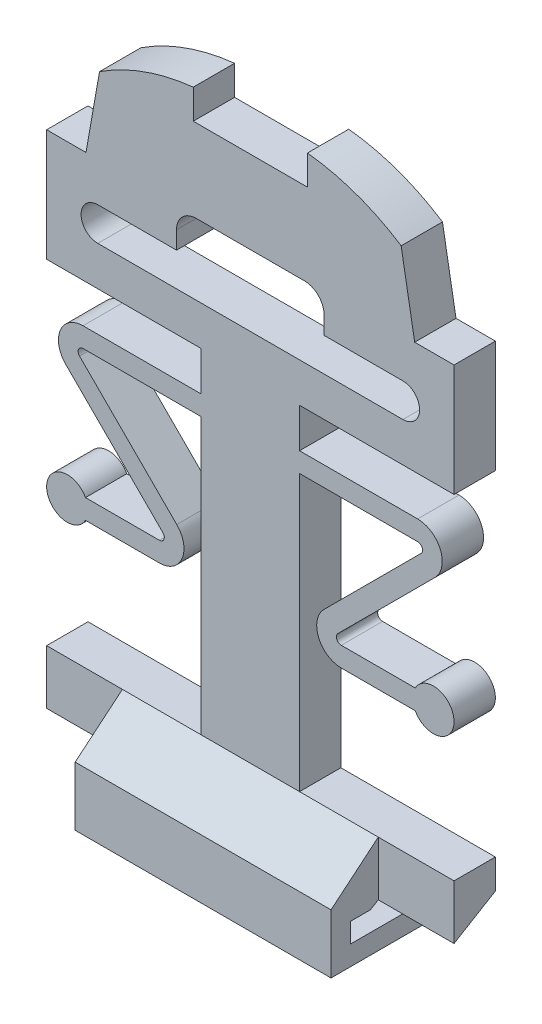
SolidWorks part; units mm, degrees
ref_plane "Ön Düzlem" through (0, 0, 0) normal (0, 0, 1) x (1, 0, 0)
ref_plane "Üst Düzlem" through (0, 0, 0) normal (0, 1, 0) x (1, 0, 0)
ref_plane "Sağ Düzlem" through (0, 0, 0) normal (1, 0, 0) x (0, 0, -1)
sketch "Çizim1" plane through (0, 0, 0) normal (0, 0, 1) x (1, 0, 0)
  line L0 (0, 58.4898) -> (0, -60.4963) construction
  line L1 (0, 0) -> (-10.35, 0)
  line L2 (-10.35, 0) -> (-10.35, 5)
  line L3 (-10.35, 5) -> (-2.5, 5)
  line L4 (-2.5, 5) -> (-2.5, 19)
  line L5 (-2.5, 20) -> (-8.5, 20)
  line L6 (-9.3839, 17.8661) -> (-4.4445, 12.9268)
  line L7 (-4.6213, 12.5) -> (-8.3767, 12.5)
  line L8 (-2.5, 19) -> (-8.5, 19)
  line L9 (-8.6768, 18.5732) -> (-3.7374, 13.6339)
  line L10 (-4.6213, 11.5) -> (-8.3767, 11.5)
  line L11 (-10.35, 5) -> (-10.35, 12) construction
  line L12 (-2.5, 19) -> (-2.5, 20) construction
  line L13 (-2.5, 20) -> (-2.5, 22)
  line L14 (-2.5, 22) -> (-10.35, 22)
  line L15 (-10.35, 22) -> (-10.35, 27.7)
  line L16 (-10.35, 27.7) -> (-8.35, 27.7)
  line L17 (-8.35, 27.7) -> (-7.6623, 31.6)
  line L18 (-2.9, 33.3) -> (0, 33.3) construction
  line L19 (-2.9, 33.3) -> (-2.9, 31.8)
  line L20 (-2.9, 31.8) -> (0, 31.8)
  line L21 (0, 31.8) -> (0, 27.6)
  line L22 (-10.35, 24.85) -> (0, 24.85) construction
  line L23 (0, 24) -> (-7.75, 24)
  line L24 (-7.75, 25.7) -> (-3.75, 25.7)
  line L25 (-3.75, 25.7) -> (-3.75, 26.6)
  line L26 (-2.75, 27.6) -> (0, 27.6)
  line L27 (0, 24) -> (0, 0)
  arc A0 (-8.5, 20) -> (-9.3839, 17.8661) centre (-8.5, 18.75) ccw
  arc A1 (-4.4445, 12.9268) -> (-4.6213, 12.5) centre (-4.6213, 12.75) cw
  arc A2 (-8.5, 19) -> (-8.6768, 18.5732) centre (-8.5, 18.75) ccw
  arc A3 (-3.7374, 13.6339) -> (-4.6213, 11.5) centre (-4.6213, 12.75) cw
  arc A4 (-8.3767, 12.5) -> (-8.3767, 11.5) centre (-9.3, 12) ccw
  arc A5 (-7.6623, 31.6) -> (-2.9, 33.3) centre (-1.7512, 22.5613) cw
  arc A6 (-7.75, 25.7) -> (-7.75, 24) centre (-7.75, 24.85) ccw
  arc A7 (-3.75, 26.6) -> (-2.75, 27.6) centre (-2.75, 26.6) cw
  dimension "D3" = 1.25
  dimension "D5" = 2.1
  dimension "D7" = 0.25
  dimension "D12" = 5
  dimension "D13" = 1.25
  dimension "D21" = 5.8
  dimension "D23" = 10.8
  dimension "D25" = 7.75
  dimension "D28" = 1
  dimension "D1" = 5
  dimension "D2" = 15
  dimension "D4" = 45
  dimension "D6" = 20.7
  dimension "D9" = 8.5
  dimension "D8" = 6
  dimension "D10" = 1
  dimension "D11" = 1
  dimension "D14" = 5.7
  dimension "D15" = 2
  dimension "D16" = 11.3
  dimension "D17" = 20.7
  dimension "D18" = 2
  dimension "D19" = 9.6
  dimension "D20" = 100
  dimension "D22" = 31.8
  dimension "D24" = 0.85
  dimension "D26" = 1.7
  dimension "D27" = 3.6
  dimension "D29" = 3.75
extrude "Yükseklik-Ekstrüzyon2" add sketch "Çizim1" along normal blind 2.1 contours L17 A5 L19 L20 L21 L26 A7 L25 L24 A6 L23 L27 L1 L2 L3 L4 L8 A2 L9 A3 L10 A4 L7 A1 L6 A0 L5 L13 L14 L15 L16
sketch "Çizim2" plane through (0, 0, 0) normal (1, 0, 0) x (0, 0, -1)
  line L0 (-2.1, 5) -> (-4.5, 3)
  line L1 (-4.5, 3) -> (-4.5, 0)
  line L2 (-4.5, 0) -> (2.5, 0)
  line L3 (2.5, 0) -> (2.5, 1)
  line L4 (2.5, 1) -> (-3.5, 1)
  line L5 (-3.5, 1) -> (-3.5, 2)
  line L6 (-3.5, 2) -> (-2.5, 2)
  line L7 (-2.5, 2) -> (0, 3.5)
  line L8 (0, 0) -> (0, 5) construction
  line L9 (-2.1, 5) -> (0, 5) construction
  line L10 (-2.1, 5) -> (0, 5)
  line L11 (0, 24) -> (0, 0) construction
  line L12 (0, 5) -> (0, 3.5)
  line L13 (0, 3.5) -> (2.5, 1)
  dimension "D1" = 4.5
  dimension "D2" = 3
  dimension "D3" = 7
  dimension "D4" = 1
  dimension "D5" = 1
  dimension "D6" = 1.5
  dimension "D7" = 1
  dimension "D8" = 1
extrude "Yükseklik-Ekstrüzyon3" add sketch "Çizim2" against normal through all contours L12 L10 L0 L1 L2 L3 L4 L5 L6 L7 region at (0, 4.914, 1.05)
extrude "Kes-Ekstrüzyon1" cut sketch "Çizim2<3>" against normal through all contours L13 L7 L6 L5 L4 region at (0, 1.8431, 0.598)
sketch "Çizim2<3>" plane through (0, 0, 0) normal (1, 0, 0) x (0, 0, -1) same geometry as "Çizim2"
sketch "Çizim3" plane through (-10.35, 0, 0) normal (-1, 0, 0) x (0, 0, 1)
  line L0 (2.1, 5) -> (2.1, 2.24)
  line L10 (3.5, 1) -> (-2.5, 1)
  line L11 (-2.5, 1) -> (-2.5, 0)
  line L12 (-2.5, 0) -> (4.5, 0)
  line L13 (4.5, 0) -> (4.5, 3)
  line L14 (4.5, 3) -> (2.1, 5)
  line L15 (2.1, 5) -> (0, 5)
  line L16 (0, 5) -> (0, 3.5)
  line L17 (0, 3.5) -> (2.5, 2)
  line L18 (2.5, 2) -> (3.5, 2)
  line L19 (3.5, 2) -> (3.5, 1)
  line L20 (3.5, 1) -> (-2.5, 1)
  line L21 (-2.5, 1) -> (-2.5, 0)
  line L22 (-2.5, 0) -> (4.5, 0)
  line L23 (4.5, 0) -> (4.5, 3)
  line L24 (4.5, 3) -> (2.1, 5)
  line L25 (2.1, 5) -> (0, 5)
  line L26 (0, 5) -> (0, 3.5)
  line L27 (0, 3.5) -> (2.5, 2)
  line L28 (2.5, 2) -> (3.5, 2)
  line L29 (3.5, 2) -> (3.5, 1)
  line M11 (3.5, 1) -> (-2.5, 1)
  line M12 (-2.5, 1) -> (-2.5, 0)
  line M13 (-2.5, 0) -> (4.5, 0)
  line M14 (4.5, 0) -> (4.5, 3)
  line M15 (4.5, 3) -> (2.1, 5)
  line M18 (0, 3.5) -> (2.5, 2)
  line M19 (2.5, 2) -> (3.5, 2)
  line M20 (3.5, 2) -> (3.5, 1)
  dimension "D1" = 0
extrude "Kes-Ekstrüzyon2" cut sketch "Çizim3" against normal blind 3.85 contours L0 M15 M18 M19 M20 M11 M12 M13 M14 region at (-10.35, 3.9339, 3.2449)
mirror "Aynalama1" about plane through (0, 24, 2.1) normal (1, 0, 0) of bodies 105
